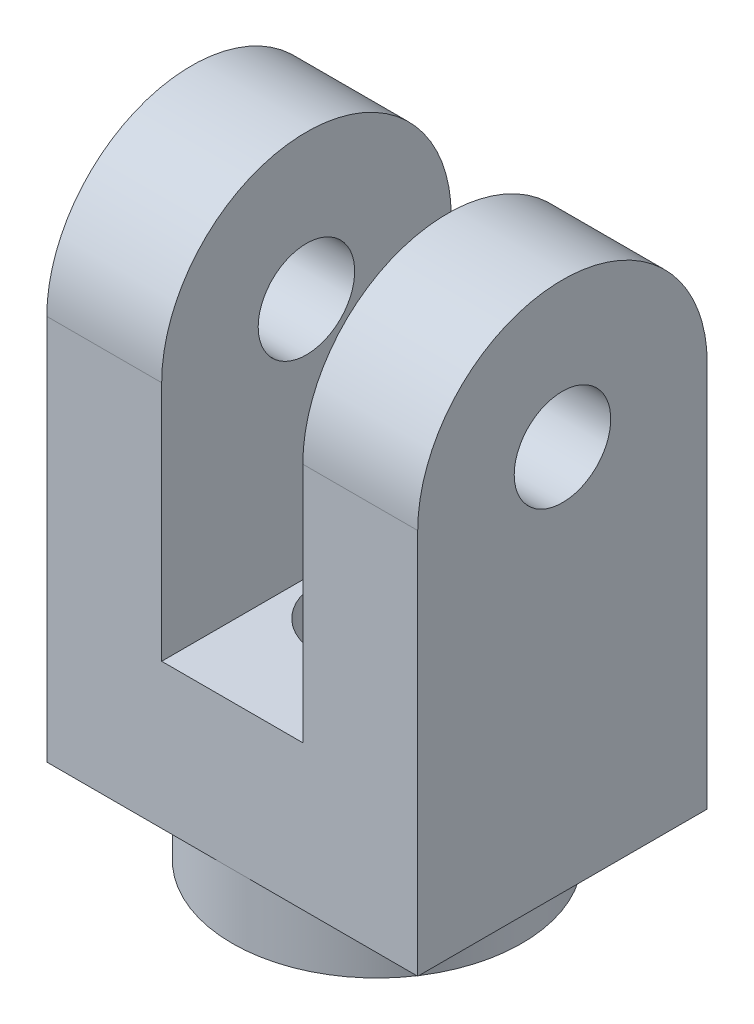
SolidWorks part; units mm, degrees
material "AISI Type 316L stainless steel"
ref_plane "Front Plane" through (0, 0, 0) normal (0, 0, 1) x (1, 0, 0)
ref_plane "Top Plane" through (0, 0, 0) normal (0, 1, 0) x (1, 0, 0)
ref_plane "Right Plane" through (0, 0, 0) normal (1, 0, 0) x (0, 0, -1)
sketch "Sketch1" plane through (0, 0, 0) normal (0, 1, 0) x (1, 0, 0)
  line L1 (-46.125, 36) -> (46.125, 36)
  line L2 (-46.125, 36) -> (-46.125, -36)
  line L3 (-46.125, -36) -> (46.125, -36)
  line L4 (46.125, 36) -> (46.125, -36)
  line L5 (-46.125, 36) -> (46.125, -36) construction
  line L6 (-46.125, -36) -> (46.125, 36) construction
  circle A0 centre (0, 0) radius 36
  circle A1 centre (0, 0) radius 15
  point P0 (0, 0)
  dimension "D3" = 30
  dimension "D1" = 92.25
  dimension "D2" = 72
extrude "Boss-Extrude1" add sketch "Sketch1" along normal blind 36 contours A0 L1 L2 L3 | A0 | A0 L3 L4 L1 region at (-23.0625, 0, -35.1449) region at (23.0625, 0, -35.1449) region at (24.7358, 0, -24.7358)
extrude "Boss-Extrude2" add sketch "Sketch1<3>" against normal blind 16 contours A0 A1 region at (24.7358, 0, -24.7358)
sketch "Sketch1<3>" plane through (0, 0, 0) normal (0, 1, 0) x (1, 0, 0) same geometry as "Sketch1"
sketch "Sketch2" plane through (-46.125, 0, 0) normal (-1, 0, 0) x (0, 0, 1)
  line L0 (-36, 36) -> (36, 36)
  line L2 (-36, 36) -> (-36, 96)
  line L4 (36, 36) -> (36, 96)
  arc A0 (36, 96) -> (-36, 96) centre (0, 96) ccw
  circle A1 centre (0, 96) radius 12
  dimension "D1" = 72
  dimension "D2" = 24
extrude "Boss-Extrude3" add sketch "Sketch2" against normal blind 28.575
mirror "Mirror1" about plane through (0, 0, 0) normal (1, 0, 0) of "Boss-Extrude1", "Boss-Extrude3"
